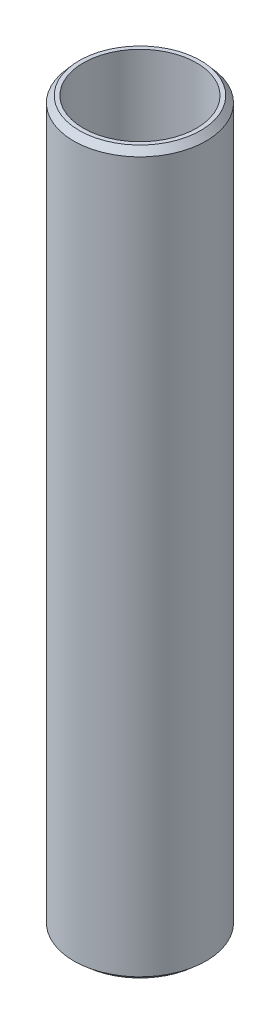
SolidWorks part; units mm, degrees
ref_plane "Front Plane" through (0, 0, 0) normal (0, 0, 1) x (1, 0, 0)
ref_plane "Top Plane" through (0, 0, 0) normal (0, 1, 0) x (1, 0, 0)
ref_plane "Right Plane" through (0, 0, 0) normal (1, 0, 0) x (0, 0, -1)
sketch "Sketch1" plane through (0, 0, 0) normal (0, 1, 0) x (1, 0, 0)
  circle A0 centre (0, 0) radius 55
  dimension "SHAFT_OD" = 110
extrude "Boss-Extrude1" add sketch "Sketch1" along normal blind 600
sketch "Sketch2" plane through (0, 0, 0) normal (0, 1, 0) x (1, 0, 0)
  circle A0 centre (0, 0) radius 47.0655
  dimension "BORE_D" = 94.131
extrude "Cut-Extrude1" cut sketch "Sketch2" along normal through all
chamfer "Chamfer1" distance 5.2797 angle 40.965 2 edges at (0, 600, 55) (0, 0, 55) first distance on face at (0, 600, 55) first distance on face at (0, 0, 47.0655)
